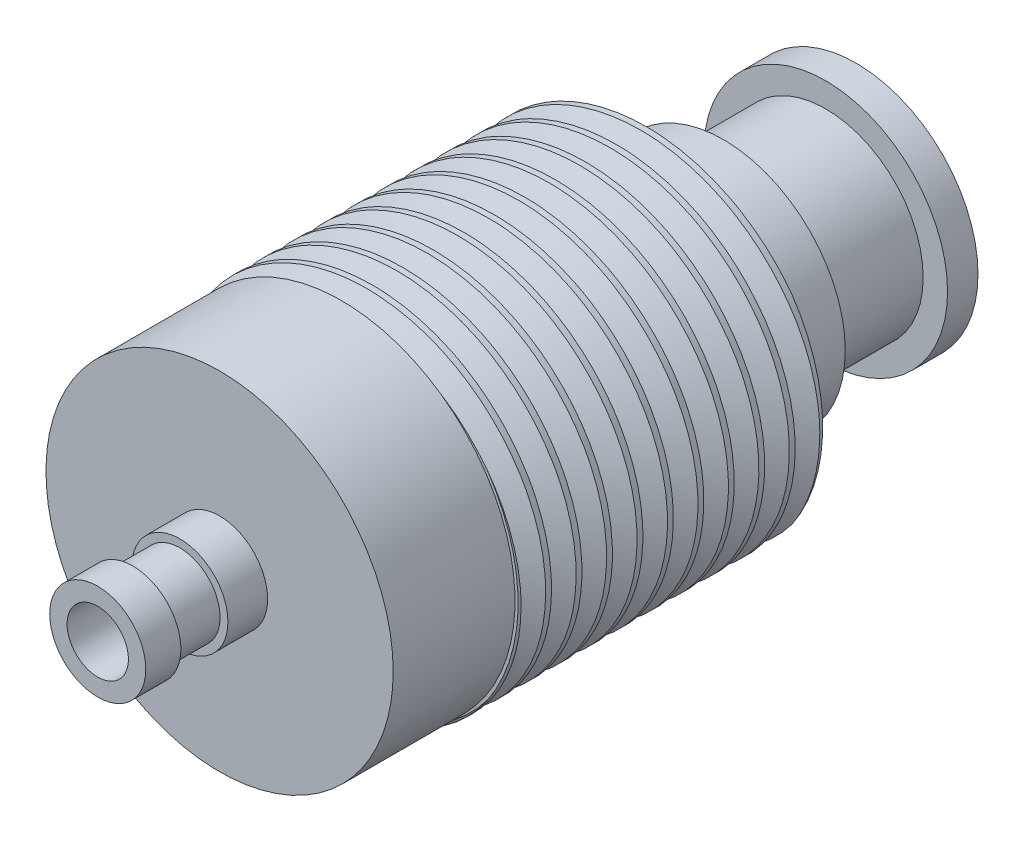
SolidWorks part; units mm, degrees
ref_plane "Plan de face" through (0, 0, 0) normal (0, 0, 1) x (1, 0, 0)
ref_plane "Plan de dessus" through (0, 0, 0) normal (0, 1, 0) x (1, 0, 0)
ref_plane "Plan de droite" through (0, 0, 0) normal (1, 0, 0) x (0, 0, -1)
sketch "Esquisse1" plane through (0, 0, 0) normal (0, 0, 1) x (1, 0, 0)
  circle A0 centre (0, 0) radius 2
extrude "Boss.-Extru.1" add sketch "Esquisse1" along normal blind 0.5
sketch "Esquisse2" plane through (0, 0, 0.5) normal (0, 0, 1) x (1, 0, 0)
  circle A0 centre (0, 0) radius 1.6
extrude "Boss.-Extru.2" add sketch "Esquisse2" along normal blind 1.5
sketch "Esquisse3" plane through (0, 0, 2) normal (0, 0, 1) x (1, 0, 0)
  circle A0 centre (-0.1789, -0.1762) radius 2
extrude "Boss.-Extru.3" add sketch "Esquisse3" along normal blind 1.45
sketch "Esquisse4" plane through (0, 0, 3.45) normal (0, 0, 1) x (1, 0, 0)
  circle A0 centre (0, 0) radius 2.9
extrude "Boss.-Extru.4" add sketch "Esquisse4" along normal blind 5
sketch "Esquisse5" plane through (0, 0, 8.45) normal (0, 0, 1) x (1, 0, 0)
  circle A1 centre (0, 0) radius 2.9
  circle A2 centre (0, 0) radius 2.9
  dimension "D1" = 0
curve "Hélice/Spirale1" pitch 0.5 height 5 turns 10
sketch "Esquisse8" plane through (0, 0, 0) normal (0, 1, 0) x (1, 0, 0)
  line L1 (-2.55, -8.45) -> (-3.075, -8.1469)
  line L2 (-3.075, -8.1469) -> (-3.075, -8.7531)
  line L3 (-3.075, -8.7531) -> (-2.55, -8.45)
  circle A0 centre (-2.9, -8.45) radius 0.175 construction
sweep "Enlèvement de matière-Balayage1" cut profiles "Esquisse8" path "Hélice/Spirale1" align with end faces yes
sketch "Esquisse9" plane through (0, 0, 8.45) normal (0, 0, 1) x (1, 0, 0)
  circle A0 centre (0, 0) radius 2.85
extrude "Boss.-Extru.5" add sketch "Esquisse9" along normal blind 2
sketch "Esquisse10" plane through (0, 0, 10.45) normal (0, 0, 1) x (1, 0, 0)
  circle A0 centre (0, 0) radius 0.7884
extrude "Boss.-Extru.6" add sketch "Esquisse10" along normal blind 2
sketch "Esquisse11" plane through (0, 0, 12.45) normal (0, 0, 1) x (1, 0, 0)
  circle A0 centre (0, 0) radius 0.5035
extrude "Enlèv. mat.-Extru.1" cut sketch "Esquisse11" against normal blind 35
sketch "Esquisse12" plane through (0, 0, 0) normal (1, 0, 0) x (0, 0, -1)
  line L0 (-13.1242, 0) -> (-8.3235, 0) construction
  line L1 (-11.8737, 0.9096) -> (-11.1017, 0.9096)
  line L2 (-11.8737, 0.9096) -> (-11.8737, 0.6596)
  line L3 (-11.8737, 0.6596) -> (-11.1017, 0.6596)
  line L4 (-11.1017, 0.9096) -> (-11.1017, 0.6596)
  dimension "D1" = 0.25
revolve "Enlèvement de matière-Révolution4" cut sketch "Esquisse12" angle 360 about L0
